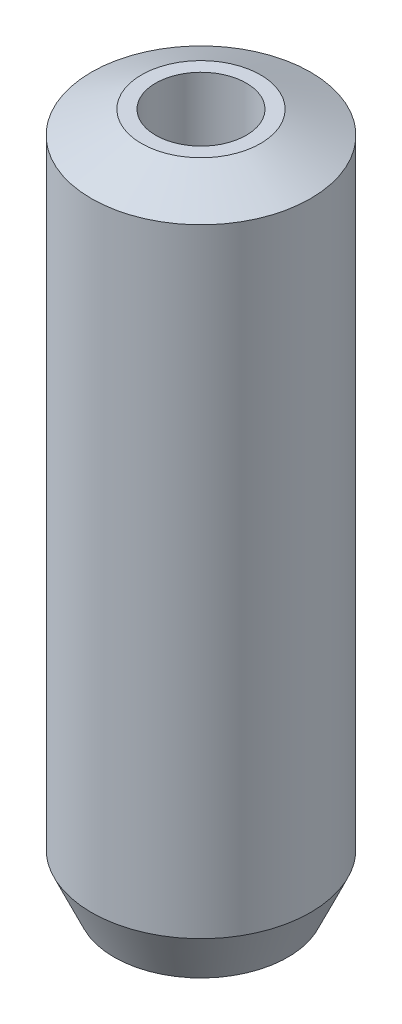
SolidWorks part; units mm, degrees
ref_plane "Front Plane" through (0, 0, 0) normal (0, 0, 1) x (1, 0, 0)
ref_plane "Top Plane" through (0, 0, 0) normal (0, 1, 0) x (1, 0, 0)
ref_plane "Right Plane" through (0, 0, 0) normal (1, 0, 0) x (0, 0, -1)
sketch "Sketch1" plane through (0, 0, 0) normal (0, 1, 0) x (1, 0, 0)
  circle A0 centre (0, 0) radius 15
  dimension "SHAFT_OD" = 30
extrude "Boss-Extrude1" add sketch "Sketch1" along normal blind 94.5937
sketch "Sketch2" plane through (0, 0, 0) normal (0, 1, 0) x (1, 0, 0)
  circle A0 centre (0, 0) radius 6.1986
  dimension "BORE_D" = 12.3973
extrude "Cut-Extrude1" cut sketch "Sketch2" along normal through all
chamfer "Chamfer1" distance 3.1013 angle 65.648 2 edges at (0, 94.5937, 15) (0, 0, 15) first distance on face at (0, 94.5937, 15) first distance on face at (0, 0, 6.1986)
